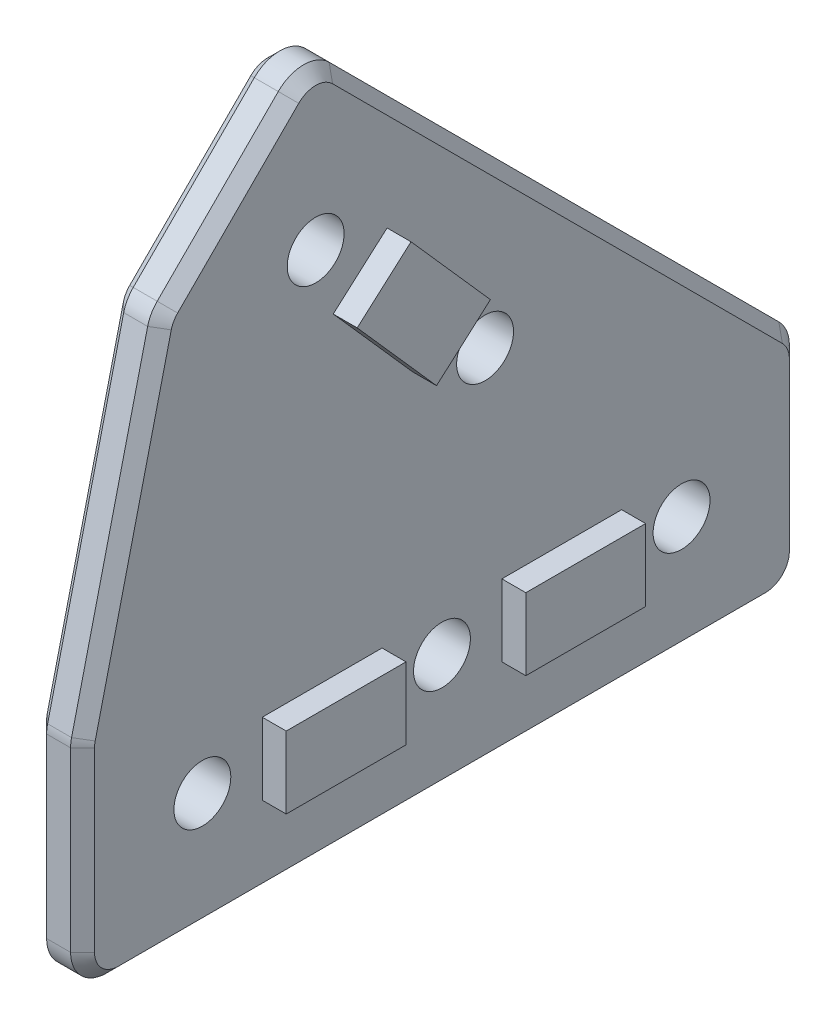
SolidWorks part; units mm, degrees
material "Chrome Stainless Steel"
ref_plane "Front Plane" through (0, 0, 0) normal (0, 0, 1) x (1, 0, 0)
ref_plane "Top Plane" through (0, 0, 0) normal (0, 1, 0) x (1, 0, 0)
ref_plane "Right Plane" through (0, 0, 0) normal (1, 0, 0) x (0, 0, -1)
sketch "Sketch1" plane through (0, 0, 0) normal (1, 0, 0) x (0, 0, -1)
  line L0 (0, 0) -> (-350, 350) construction
  line L1 (-350, 350) -> (-350, 0) construction
  line L2 (-350, 0) -> (0, 0) construction
  line L3 (-78.1401, 0) -> (-18.1401, 0)
  line L4 (-18.1401, 0) -> (-18.1401, 18.1401)
  line L5 (-18.1401, 18.1401) -> (-58.6831, 58.6831)
  line L6 (-58.6831, 58.6831) -> (-71.5101, 45.8561)
  line L7 (-78.1401, 0) -> (-78.1401, 18.1401)
  line L8 (-78.1401, 18.1401) -> (-71.5101, 45.8561)
  dimension "D1" = 350
  dimension "D2" = 350
  dimension "D3" = 60
extrude "Boss-Extrude1" add sketch "Sketch1" along normal blind 4
sketch "Sketch2" plane through (4, 0, 0) normal (1, 0, 0) x (0, 0, -1)
  line L0 (-78.1401, 0) -> (-18.1401, 0) construction
  line L1 (-18.1401, 18.1401) -> (-58.6831, 58.6831) construction
  line L2 (-58.6831, 58.6831) -> (-71.5101, 45.8561) construction
  line L5 (-18.1401, 0) -> (-18.1401, 18.1401) construction
  circle A0 centre (-28.1401, 10) radius 2.375
  circle A1 centre (-58.6831, 44.5409) radius 2.375
  dimension "D1" = 4.75
  dimension "D3" = 4.75
  dimension "D2" = 10
  dimension "D4" = 10
  dimension "D5" = 10
  dimension "D6" = 10
extrude "Cut-Extrude1" cut sketch "Sketch2" against normal through all contours A0 region at (4, 10, 28.1401)
pattern_linear "LPattern1" count 3 spacing 20 along (0, 0, 1) of "Cut-Extrude1"
extrude "Cut-Extrude2" cut sketch "Sketch2<4>" against normal through all contours A1 region at (4, 44.5409, 58.6831)
sketch "Sketch2<4>" plane through (4, 0, 0) normal (1, 0, 0) x (0, 0, -1) same geometry as "Sketch2"
pattern_linear "LPattern2" count 2 spacing 20 along (0, -0.7071, -0.7071) of "Cut-Extrude2"
fillet "Fillet1" radius 3 6 edges at (2, 0, 18.1401) (2, 18.1401, 18.1401) (2, 58.6831, 58.6831) (2, 0, 78.1401) (2, 18.1401, 78.1401) (2, 45.8561, 71.5101)
chamfer "Chanfro1" distance 1 angle 45 24 edges at (4, 0, 48.1401) (4, 0.8787, 19.0188) (4, 0.8787, 77.2614) (4, 9.9487, 18.1401) (4, 10.3931, 78.1401) (4, 18.0455, 18.3685) (4, 18.1377, 78.1195) (4, 37.7903, 37.7903) (4, 31.7581, 74.8825) (4, 45.7988, 71.4076) (4, 57.4404, 58.6831) (4, 51.5085, 65.8576) (0, 0, 48.1401) (0, 0.8787, 19.0188) (0, 0.8787, 77.2614) (0, 9.9487, 18.1401) (0, 10.3931, 78.1401) (0, 18.0455, 18.3685) (0, 18.1377, 78.1195) (0, 37.7903, 37.7903) (0, 31.7581, 74.8825) (0, 57.4404, 58.6831) (0, 45.7988, 71.4076) (0, 51.5085, 65.8576)
sketch "Esboço1" plane through (4, 0, 0) normal (1, 0, 0) x (0, 0, -1)
  line L0 (-68.1401, 10) -> (-28.1401, 10) construction
  line L1 (-58.6831, 44.5409) -> (-48.7568, 33.3153) construction
  line L2 (-57.2167, 39.1834) -> (-50.5924, 31.6921)
  line L3 (-63.1401, 13) -> (-53.1401, 13)
  line L4 (-63.1401, 13) -> (-63.1401, 7)
  line L5 (-63.1401, 7) -> (-53.1401, 7)
  line L6 (-53.1401, 13) -> (-53.1401, 7)
  line L7 (-63.1401, 13) -> (-53.1401, 7) construction
  line L8 (-63.1401, 7) -> (-53.1401, 13) construction
  line L9 (-43.1401, 13) -> (-33.1401, 13)
  line L10 (-43.1401, 13) -> (-43.1401, 7)
  line L11 (-43.1401, 7) -> (-33.1401, 7)
  line L12 (-33.1401, 13) -> (-33.1401, 7)
  line L13 (-43.1401, 13) -> (-33.1401, 7) construction
  line L14 (-43.1401, 7) -> (-33.1401, 13) construction
  line L15 (-57.2167, 39.1834) -> (-52.7219, 43.1579)
  line L16 (-50.5924, 31.6921) -> (-46.0977, 35.6666)
  line L17 (-52.7219, 43.1579) -> (-46.0977, 35.6666)
  line L18 (-57.2167, 39.1834) -> (-46.0977, 35.6666) construction
  line L19 (-50.5924, 31.6921) -> (-52.7219, 43.1579) construction
  circle A0 centre (-68.1401, 10) radius 2.375 construction
  circle A2 centre (-48.1401, 10) radius 2.375 construction
  circle A4 centre (-44.5409, 30.3988) radius 2.375 construction
  point P5 (-58.1401, 10)
  point P11 (-38.1401, 10)
  point P17 (-51.6572, 37.425)
  point P18 (-36.1829, 20.4417)
  dimension "D5" = 10
  dimension "D1" = 6
  dimension "D2" = 6
  dimension "D4" = 6
  dimension "D7" = 10
  dimension "D8" = 10
  dimension "D9" = 5
  dimension "D10" = 5
  dimension "D11" = 13
  dimension "D12" = 10
extrude "Ressalto-extrusão1" add sketch "Esboço1" along normal blind 2
equation "\"D1@Sketch2\"=\"D3@Sketch2\""
equation "\"D2@Esboço1\"=\"D1@Esboço1\""
equation "\"D4@Esboço1\"=\"D1@Esboço1\""
